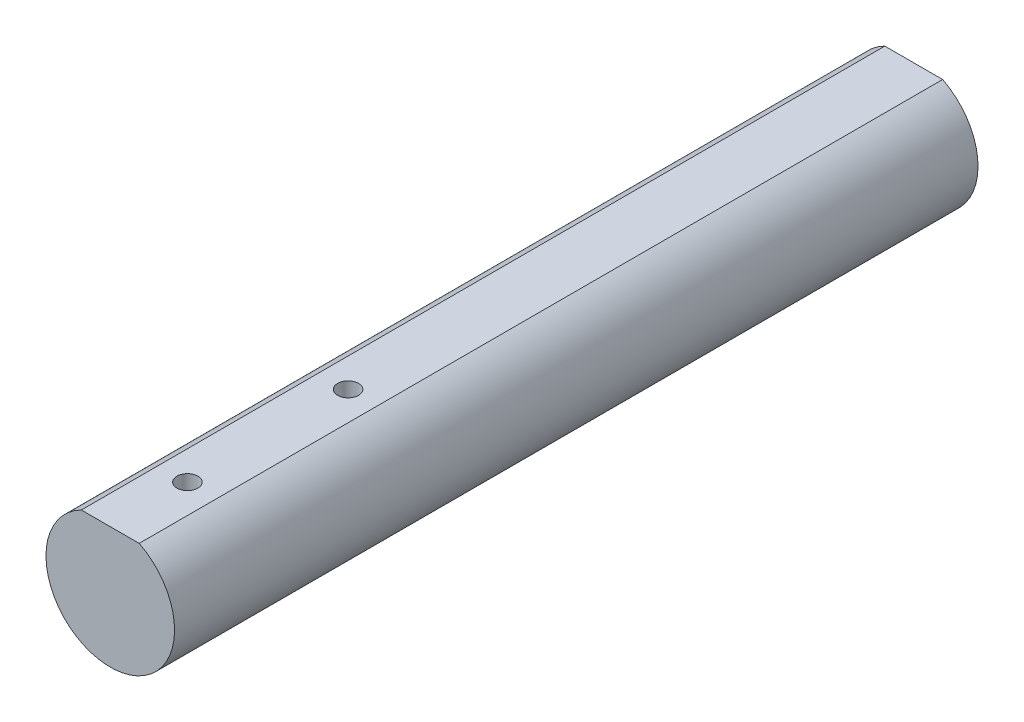
SolidWorks part; units mm, degrees
ref_plane "Front Plane" through (0, 0, 0) normal (0, 0, 1) x (1, 0, 0)
ref_plane "Top Plane" through (0, 0, 0) normal (0, 1, 0) x (1, 0, 0)
ref_plane "Right Plane" through (0, 0, 0) normal (1, 0, 0) x (0, 0, -1)
sketch "Sketch1" plane through (0, 0, 0) normal (0, 0, 1) x (1, 0, 0)
  circle A0 centre (0, 0) radius 10
  dimension "D1" = 20
extrude "Boss-Extrude1" add sketch "Sketch1" along normal mid plane 125
sketch "Sketch2" plane through (0, 0, 62.5) normal (0, 0, 1) x (1, 0, 0)
  line L0 (0, -1000) -> (0, 49000) construction
  line L1 (-4.5, 13.9303) -> (4.5, 13.9303)
  line L2 (-4.5, 13.9303) -> (-4.5, 8.9303)
  line L3 (-4.5, 8.9303) -> (4.5, 8.9303)
  line L4 (4.5, 13.9303) -> (4.5, 8.9303)
  line L5 (-4.5, 13.9303) -> (4.5, 8.9303) construction
  line L6 (-4.5, 8.9303) -> (4.5, 13.9303) construction
  circle A0 centre (0, 0) radius 10 construction
  point P0 (0, 11.4303)
  dimension "D1" = 9
  dimension "D2" = 5
extrude "Cut-Extrude1" cut sketch "Sketch2" against normal through all
sketch "Sketch3" plane through (0, 8.9303, 0) normal (0, 1, 0) x (1, 0, 0)
  line L0 (0, -1000) -> (0, 49000) construction
  line L1 (-4.5, -62.5) -> (4.5, -62.5) construction
  circle A0 centre (0, -50.5) radius 1.625
  circle A1 centre (0, -25.5) radius 1.625
  dimension "D5" = 3.25
  dimension "D6" = 3.25
  dimension "D1" = 12
  dimension "D2" = 25
extrude "Cut-Extrude2" cut sketch "Sketch3" against normal through all
sketch "Sketch4" plane through (0, 8.9303, 0) normal (0, 1, 0) x (1, 0, 0)
  circle A1 centre (0, -25.5) radius 4
  circle A2 centre (0, -50.5) radius 4
  dimension "D2" = 8
  dimension "D3" = 8
extrude "Cut-Extrude3" cut sketch "Sketch4" against normal blind 150 from offset 8 offset against normal yes
